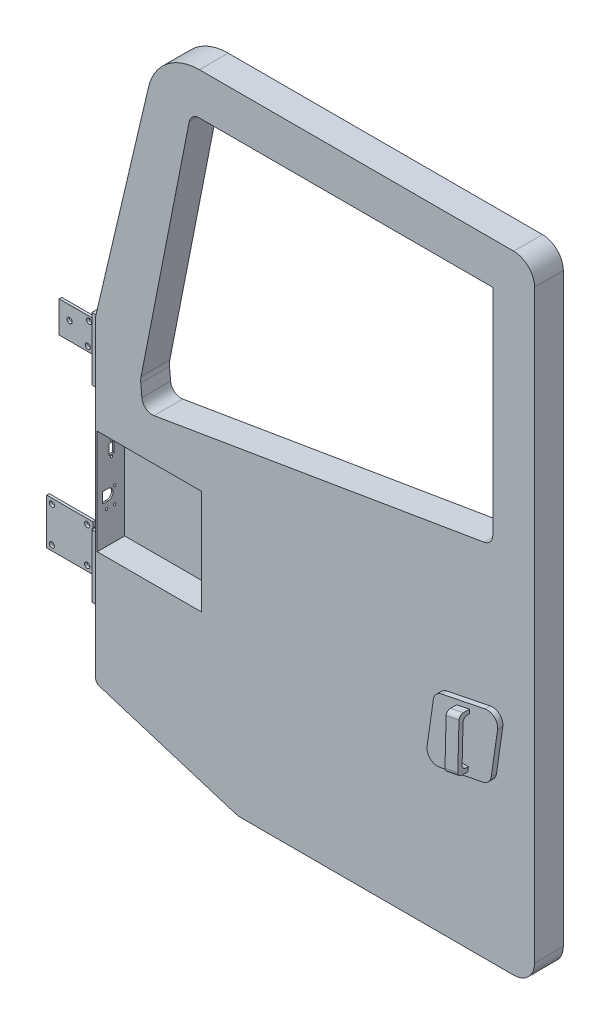
SolidWorks part; units mm, degrees
ref_plane "Front Plane" through (0, 0, 0) normal (0, 0, 1) x (1, 0, 0)
ref_plane "Top Plane" through (0, 0, 0) normal (0, 1, 0) x (1, 0, 0)
ref_plane "Right Plane" through (0, 0, 0) normal (1, 0, 0) x (0, 0, -1)
sketch "Sketch2" plane through (0, 0, 0) normal (0, 0, 1) x (1, 0, 0)
  line L1 (-179.7693, -762.022) -> (482.6, -762.022)
  line L3 (-281.2299, 761.978) -> (482.6, 761.978)
  line L4 (533.4, -711.222) -> (533.4, 711.178)
  line L5 (-459.8603, -656.939) -> (-452.0517, -645.784) construction
  line L6 (-417.9715, 597.0829) -> (44.2876, -63.266) construction
  line L8 (-524.4721, -657.2008) -> (-194.8579, -759.7295)
  line L9 (-306.1723, 639.7777) -> (-423.0219, 45.4039)
  line L10 (-423.7768, 31.1096) -> (-421.1458, 1.4921)
  line L14 (-281.2299, 660.378) -> (431.8, 660.378)
  line L16 (431.7996, 138.4174) -> (431.8, 660.378)
  line L17 (431.8, -660.422) -> (431.8, 660.378) construction
  line L18 (-172.0509, -660.422) -> (431.8, -660.422) construction
  line L19 (-533.4, 116.926) -> (-405.8883, 659.253)
  line L20 (-367.7549, -599.547) -> (-172.0509, -660.422) construction
  line L21 (-55.7209, -79.6007) -> (521.0599, 744.3665) construction
  line L22 (-306.1723, 639.7777) -> (-424.4164, 38.3105) construction
  line L23 (-424.4164, 38.3105) -> (-367.7549, -599.547) construction
  line L24 (-414.3579, -691.4526) -> (-194.8579, -759.7295) construction
  line L25 (-179.7693, -762.022) -> (482.6, -762.022)
  line L27 (-281.2299, 761.978) -> (482.6, 761.978)
  line L28 (533.4, -711.222) -> (533.4, 711.178)
  line L29 (-459.8603, -656.939) -> (-452.0517, -645.784) construction
  line L30 (-417.9715, 597.0829) -> (44.2876, -63.266) construction
  line L31 (-533.4, 116.926) -> (-466.2749, -638.723) construction
  line L32 (-391.6402, -21.3099) -> (410.6048, 113.3679)
  line L33 (-55.7209, -79.6007) -> (521.0599, 744.3665) construction
  line L34 (-281.2299, 761.978) -> (482.6, 761.978)
  line L35 (-533.4, 116.926) -> (-533.4, -645.074)
  line L36 (-179.7693, -762.022) -> (482.6, -762.022)
  line L37 (533.4, 711.178) -> (533.4, -711.222)
  line L38 (-417.9715, 597.0829) -> (44.2876, -63.266) construction
  line L39 (-471.5639, -673.6583) -> (-452.0517, -645.784) construction
  line L40 (-405.8883, 659.253) -> (-528.8132, 33.9764) construction
  line L41 (-55.7209, -79.6007) -> (521.0599, 744.3665) construction
  arc A0 (-405.8883, 659.253) -> (-281.2299, 761.978) centre (-281.2299, 634.978) cw
  arc A3 (533.4, 711.178) -> (482.6, 761.978) centre (482.6, 711.178) ccw
  arc A4 (482.6, -762.022) -> (533.4, -711.222) centre (482.6, -711.222) ccw
  arc A5 (-194.8579, -759.7295) -> (-179.7693, -762.022) centre (-179.7693, -711.222) ccw
  arc A7 (-367.7549, -599.547) -> (-367.7549, -599.547) centre (-367.7549, -599.547) ccw
  arc A8 (-172.0509, -660.422) -> (-172.0509, -660.422) centre (-172.0509, -660.422) ccw
  arc A9 (431.8, -660.422) -> (431.8, -660.422) centre (431.8, -660.422) ccw
  arc A10 (431.8, 660.378) -> (431.8, 660.378) centre (431.8, 660.378) ccw
  arc A11 (-306.1723, 639.7777) -> (-281.2299, 660.378) centre (-281.2299, 634.978) cw
  arc A12 (-423.0219, 45.4039) -> (-423.7768, 31.1096) centre (-373.176, 35.6045) ccw
  arc A13 (-424.4164, 38.3105) -> (-424.4164, 38.3105) centre (-424.4164, 38.3105) ccw construction
  arc A16 (-466.2749, -638.723) -> (-414.3579, -691.4526) centre (-391.0208, -616.5518) ccw construction
  arc A17 (-533.4, -645.074) -> (-524.4721, -657.2008) centre (-520.7, -645.074) ccw
  arc A18 (-528.8132, 33.9764) -> (-533.4, 116.926) centre (-501.9071, 77.0658) ccw construction
  arc A19 (431.7996, 138.4174) -> (410.6048, 113.3679) centre (406.3996, 138.4174) cw
  arc A20 (-391.6402, -21.3099) -> (-421.1458, 1.4921) centre (-395.8454, 3.7395) cw
  point P0 (0, 0)
  point P16 (-533.4, -0.0244)
  point P56 (0, 0)
  point P61 (0, 0)
  dimension "D3" = 127
  dimension "D6" = 50.8
  dimension "D8" = 50.8
  dimension "D2" = 12.7
  dimension "D9" = 25.4
  dimension "D1" = 1066.8
  dimension "D4" = 1524
  dimension "D5" = 762
  dimension "D7" = 101.6
extrude "Boss-Extrude1" add sketch "Sketch2" along normal mid plane 69.85 contours L8 A5 L1 A4 L4 A3 L3 A0 L10 A12 L9 A11 L14 L16 A20 region at (22.1716, -171.0663, 0)
ref_plane "bottom" through (0, -762.022, 0) normal (0, -1, 0) x (-1, 0, 0)
ref_plane "top door check" through (0, -158.772, 0) normal (0, -1, 0) x (-1, 0, 0)
ref_plane "door check mid" through (0, -176.2345, 0) normal (0, -1, 0) x (-1, 0, 0)
ref_plane "bottom door check" through (0, -193.697, 0) normal (0, -1, 0) x (-1, 0, 0)
ref_plane "top hinge top hole" through (0, 66.653, 0) normal (0, -1, 0) x (-1, 0, 0)
ref_plane "top hinge middle hole" through (0, 44.428, 0) normal (0, -1, 0) x (-1, 0, 0)
ref_plane "top hinge bottom hole" through (0, 12.678, 0) normal (0, -1, 0) x (-1, 0, 0)
ref_plane "bottome hinge top hole" through (0, -363.5595, 0) normal (0, -1, 0) x (-1, 0, 0)
ref_plane "bottom hinge bottom hole" through (0, -449.2845, 0) normal (0, -1, 0) x (-1, 0, 0)
ref_plane "Plane1" through (0, 0, 31.75) normal (0, 0, 1) x (1, 0, 0)
sketch "Sketch3" plane through (0, 0, 34.925) normal (0, 0, 1) x (1, 0, 0)
  line L0 (320.1959, -245.101) -> (425.9265, -223.6716)
  line L3 (314.9201, -401.6691) -> (420.6507, -380.2397)
  line L4 (456.113, -252.1835) -> (440.7462, -358.9639)
  line L5 (300.1004, -266.3768) -> (284.7336, -373.1572)
  line L6 (310.4001, -194.8067) -> (287.3499, -354.9772) construction
  line L7 (-487.6326, -408.8312) -> (533.4008, -201.8888) construction
  line L8 (-457.3598, -558.1943) -> (563.6737, -351.2518) construction
  line L9 (461.2461, -216.515) -> (438.1959, -376.6855) construction
  line L10 (373.0612, -234.3863) -> (367.7854, -390.9544) construction
  line L11 (360.2667, -236.9795) -> (354.9908, -393.5476)
  line L12 (385.8558, -231.7931) -> (380.58, -388.3612)
  line L13 (360.3684, -233.9586) -> (355.0926, -390.5267) construction
  line L14 (385.754, -234.814) -> (380.4782, -391.3821) construction
  arc A0 (300.1004, -266.3768) -> (320.1959, -245.101) centre (325.2414, -269.9949) cw
  arc A1 (284.7336, -373.1572) -> (314.9201, -401.6691) centre (309.8746, -376.7752) ccw
  arc A2 (440.7462, -358.9639) -> (420.6507, -380.2397) centre (415.6052, -355.3458) cw
  arc A3 (456.113, -252.1835) -> (425.9265, -223.6716) centre (430.972, -248.5655) ccw
  dimension "D3" = 25.4
  dimension "D1" = 152.4
  dimension "D2" = 152.4
  dimension "D4" = 12.7
  dimension "D5" = 12.7
extrude "Boss-Extrude2" add sketch "Sketch3" along normal blind 12.7 contours L5 A1 L3 L11 L0 A0 | L4 A3 L0 L12 L3 A2 | L12 L0 L11 L3 region at (325.2101, -323.7797, 34.925) region at (370.4233, -312.6704, 34.925) region at (415.6365, -301.561, 34.925)
sketch "Sketch5" plane through (0, 0, 34.925) normal (0, 0, 1) x (1, 0, 0)
  line L6 (-179.7693, -762.022) -> (482.6, -762.022)
  line L12 (-179.7693, -762.022) -> (482.6, -762.022)
  line L28 (387.9598, -243.0291) -> (384.7172, -375.8602)
  line L29 (353.4927, -382.1888) -> (356.7353, -249.3577)
  line L30 (387.9598, -243.0291) -> (356.7353, -249.3577)
  line L31 (384.7172, -375.8602) -> (353.4927, -382.1888)
  line L32 (320.1959, -245.101) -> (425.9265, -223.6716) construction
  line L33 (314.9201, -401.6691) -> (420.6507, -380.2397) construction
  line L34 (320.1959, -245.101) -> (425.9265, -223.6716) construction
  line L35 (314.9201, -401.6691) -> (420.6507, -380.2397) construction
  dimension "D2" = 11.43
  dimension "D3" = 11.43
  dimension "D1" = 0
extrude "Boss-Extrude4" add sketch "Sketch5" along normal blind 38.1 contours L31 L28 L30 L29 region at (370.7262, -312.609, 34.925)
sketch "Sketch6" plane through (393.6581, -9.61, 0) normal (0.9997, -0.0244, 0) x (0, 0, -1)
  line L9 (-47.625, -356.1994) -> (-62.865, -356.1994)
  line L10 (-62.865, -356.1994) -> (-62.865, -243.6487)
  line L11 (-62.865, -243.6487) -> (-47.625, -243.6487)
  line L12 (-47.625, -356.1994) -> (-62.865, -356.1994)
  line L13 (-62.865, -356.1994) -> (-62.865, -243.6487)
  line L14 (-62.865, -243.6487) -> (-47.625, -243.6487)
  line M5 (-47.625, -366.3594) -> (-47.625, -233.4887)
  dimension "D1" = 10.16
extrude "Cut-Extrude6" cut sketch "Sketch6" against normal through all and the other way through all contours L14 L13 L12 M5 region at (386.3385, -309.4447, 55.245)
fillet "Fillet5" radius 10.16 4 edges at (369.1049, -379.0245, 73.025) (369.4394, -365.3242, 62.865) (372.1861, -252.8071, 62.865) (372.3476, -246.1934, 73.025)
sketch "Sketch7" plane through (-533.4, 59.3738, 0) normal (1, 0, 0) x (0, 0, 1)
  line L0 (0, 821.3958) -> (0, -702.6042) construction
  line L1 (34.925, 821.3958) -> (-34.925, 821.3958) construction
  line L2 (34.925, -702.6042) -> (-34.925, -702.6042) construction
  line L4 (-31.75, -57.5522) -> (31.75, -57.5522)
  line L5 (-31.75, -57.5522) -> (-31.75, 94.8478)
  line L6 (-31.75, 94.8478) -> (31.75, 94.8478)
  line L11 (31.75, -57.5522) -> (31.75, 94.8478)
  line L12 (-31.75, -57.5522) -> (31.75, 94.8478) construction
  line L13 (-31.75, 94.8478) -> (31.75, -57.5522) construction
  line L19 (34.925, -57.5522) -> (-34.925, -57.5522) construction
  line L21 (-31.75, 552.0478) -> (31.75, 552.0478)
  line L28 (-31.75, 552.0478) -> (-31.75, 399.6478)
  line L29 (-31.75, 399.6478) -> (31.75, 399.6478)
  line L30 (31.75, 552.0478) -> (31.75, 399.6478)
  line L31 (-31.75, 552.0478) -> (31.75, 399.6478) construction
  line L32 (-31.75, 399.6478) -> (31.75, 552.0478) construction
  point P6 (0, 18.6478)
  point P13 (0, 475.8478)
  dimension "D1" = 63.5
  dimension "D2" = 152.4
  dimension "D4" = 304.8
extrude "Boss-Extrude5" add sketch "Sketch7" against normal blind 12.7
sketch "Sketch16" plane through (0, 0, 34.925) normal (0, 0, 1) x (1, 0, 0)
  line L1 (-529.59, -122.9099) -> (-529.59, -376.9099)
  line L3 (-275.59, -376.9099) -> (-275.59, -122.9099)
  line L5 (-533.4, 116.926) -> (-533.4, -645.074) construction
  line L6 (-529.59, -122.9099) -> (-275.59, -122.9099)
  line L7 (-529.59, -376.9099) -> (-275.59, -376.9099)
  dimension "D1" = 254
  dimension "D2" = 101.6
  dimension "D3" = 254
  dimension "D4" = 3.81
extrude "Cut-Extrude8" cut sketch "Sketch16" against normal blind 66.675
sketch "Sketch20" plane through (-533.4, 0, 0) normal (-1, 0, 0) x (0, 0, 1)
  line L0 (-38.4175, -176.2345) -> (38.4175, -176.2345) construction
  line L1 (-6.35, -188.9345) -> (6.35, -188.9345)
  line L2 (-6.35, -188.9345) -> (-6.35, -163.5345)
  line L3 (-6.35, -163.5345) -> (6.35, -163.5345)
  line L4 (6.35, -188.9345) -> (6.35, -163.5345)
  line L5 (-6.35, -188.9345) -> (6.35, -163.5345) construction
  line L6 (-6.35, -163.5345) -> (6.35, -188.9345) construction
  line L7 (-38.4175, -158.772) -> (38.4175, -158.772) construction
  line L8 (6.35, -176.2345) -> (-6.35, -176.2345) construction
  circle A0 centre (0, -158.772) radius 2.54
  circle A1 centre (0, -193.697) radius 2.54
  point P0 (0, -176.2345)
  dimension "D3" = 5.08
  dimension "D1" = 12.7
  dimension "D2" = 25.4
extrude "Cut-Extrude12" cut sketch "Sketch20" against normal up to surface (3.81 mm away) contours A0 | L4 L3 L2 L1 | A1 up to face at (-529.59, -249.9099, 1.5875)
sketch "Sketch21" plane through (0, 0, 0) normal (0, 0, 1) x (1, 0, 0)
  line L0 (-38.4175, 66.653) -> (38.4175, 66.653) construction
  line L1 (-202.423, 66.653) -> (-1027.3811, 66.653) construction
  line L2 (-212.5576, 44.428) -> (-1027.3811, 44.428) construction
  line L3 (-38.4175, 44.428) -> (38.4175, 44.428) construction
  line L4 (-212.5576, 12.678) -> (-1027.3811, 12.678) construction
  line L5 (-38.4175, 12.678) -> (38.4175, 12.678) construction
  line L6 (-546.1, 116.926) -> (-546.1, -35.474) construction
  line L7 (-558.8, 66.653) -> (-546.1, 66.653)
  line L8 (-558.8, 66.653) -> (-558.8, 12.678)
  line L9 (-558.8, 12.678) -> (-546.1, 12.678)
  line L10 (-546.1, 66.653) -> (-546.1, 12.678)
  line L11 (-654.05, 77.448) -> (-654.05, 1.248)
  line L12 (-654.05, 77.448) -> (-558.8, 77.448)
  line L15 (-558.8, 77.448) -> (-558.8, 12.678)
  line L16 (-654.05, 77.448) -> (-558.8, 12.678) construction
  line L17 (-654.05, 10.0872) -> (-558.8, 77.448) construction
  line L18 (-654.05, 1.248) -> (-558.8, 1.248)
  line L19 (-558.8, 12.678) -> (-558.8, 1.248)
  circle A0 centre (-584.2, 12.678) radius 6.35
  circle A1 centre (-628.65, 44.428) radius 6.35
  circle A2 centre (-581.025, 66.653) radius 6.35
  point P18 (-605.4912, 44.428)
  dimension "D2" = 12.7
  dimension "D3" = 25.4
  dimension "D4" = 69.85
  dimension "D5" = 22.225
  dimension "D6" = 95.25
  dimension "D9" = 64.77
  dimension "D1" = 12.7
  dimension "D7" = 76.2
  dimension "D8" = 33.02
extrude "Boss-Extrude8" add sketch "Sketch21" along normal mid plane 6.35 contours L19 L8 L15 L12 L11 L18 A2 A1 A0 | L10 L7 L8 L9 region at (-552.45, 39.6655, 0) region at (-606.8928, 39.2427, 0)
sketch "Sketch26" plane through (0, 0, 0) normal (0, 0, 1) x (1, 0, 0)
  line L0 (-193.6896, -363.5595) -> (-881.8717, -363.5595) construction
  line L1 (-38.4175, -363.5595) -> (38.4175, -363.5595) construction
  line L2 (-133.4597, -449.2845) -> (-881.8717, -449.2845) construction
  line L3 (-38.4175, -449.2845) -> (38.4175, -449.2845) construction
  line L4 (-625.8948, -363.5595) -> (-625.8948, -449.2845) construction
  line L5 (-625.8948, -406.422) -> (-892.4677, -406.422) construction
  line L6 (-546.1, -340.274) -> (-546.1, -492.674) construction
  line L7 (-571.5, -449.2845) -> (-546.1, -449.2845)
  line L8 (-571.5, -449.2845) -> (-571.5, -363.5595)
  line L9 (-571.5, -363.5595) -> (-546.1, -363.5595)
  line L10 (-546.1, -449.2845) -> (-546.1, -363.5595)
  line L11 (-571.5, -449.2845) -> (-546.1, -363.5595) construction
  line L12 (-571.5, -363.5595) -> (-546.1, -449.2845) construction
  point P12 (-558.8, -406.422)
  dimension "D1" = 25.4
extrude "Boss-Extrude12" add sketch "Sketch26" along normal mid plane 12.7
sketch "Sketch27" plane through (0, 0, 0) normal (0, 0, 1) x (1, 0, 0)
  line L0 (-211.2814, -363.5595) -> (-919.4505, -363.5595) construction
  line L1 (-38.4175, -363.5595) -> (38.4175, -363.5595) construction
  line L2 (-201.3631, -449.2845) -> (-928.7076, -449.2845) construction
  line L3 (-38.4175, -449.2845) -> (38.4175, -449.2845) construction
  line L4 (-571.5, -363.5595) -> (-571.5, -449.2845) construction
  line L5 (-631.7994, -363.5595) -> (-631.7994, -449.2845) construction
  line L6 (-631.7994, -406.422) -> (-919.4505, -406.422) construction
  line L8 (-684.2125, -461.9845) -> (-571.5, -461.9845)
  line L9 (-684.2125, -461.9845) -> (-684.2125, -350.8595)
  line L10 (-684.2125, -350.8595) -> (-571.5, -350.8595)
  line L11 (-571.5, -461.9845) -> (-571.5, -350.8595)
  line L12 (-684.2125, -461.9845) -> (-571.5, -350.8595) construction
  line L13 (-684.2125, -350.8595) -> (-571.5, -461.9845) construction
  circle A0 centre (-585.7875, -363.5595) radius 6.35
  circle A2 centre (-671.5125, -449.2845) radius 6.35
  circle A4 centre (-585.7875, -449.2845) radius 6.35
  circle A5 centre (-671.5125, -363.5595) radius 6.35
  point P22 (-627.8563, -406.422)
  dimension "D1" = 12.7
  dimension "D2" = 100.0125
  dimension "D3" = 14.2875
  dimension "D4" = 12.7
extrude "Boss-Extrude13" add sketch "Sketch27" along normal mid plane 6.35
sketch "Sketch28" plane through (-533.4, 0, 0) normal (-1, 0, 0) x (0, 0, 1)
  line L1 (9.225, -256.897) -> (22.225, -256.897)
  line L3 (9.225, -282.897) -> (22.225, -282.897)
  line L4 (22.225, -256.897) -> (22.225, -282.897)
  line L5 (34.925, -245.101) -> (34.925, -223.6716) construction
  line L6 (-38.4175, -193.697) -> (38.4175, -193.697) construction
  arc A6 (9.225, -256.897) -> (9.225, -282.897) centre (9.225, -269.897) ccw
  circle A7 centre (-7.705, -258.147) radius 3
  circle A8 centre (-7.705, -298.147) radius 3
  circle A9 centre (12.295, -298.147) radius 3
  point P7 (-3.775, -269.897)
  point P16 (22.225, -269.897)
  dimension "D4" = 40
  dimension "D5" = 26
  dimension "D6" = 26
  dimension "D1" = 11.75
  dimension "D2" = 3.93
  dimension "D3" = 20
  dimension "D8" = 12.7
  dimension "D7" = 6
  dimension "D9" = 13
  dimension "D10" = 76.2
extrude "Cut-Extrude13" cut sketch "Sketch28" against normal up to surface (3.81 mm away) contours L1 A6 L3 L4 | A8 | A9 | A7 region at (-533.4, -269.897, 10.4385) region at (-533.4, -298.147, -7.705) region at (-533.4, -298.147, 12.295) up to face at (-529.59, -176.2345, 0)
equation "\"doorwidth\"= 42in"
equation "\"D1@Sketch2\"=\"doorwidth\""
equation "\"doorheight\"= 60in"
equation "\"D4@Sketch2\"=\"doorheight\""
equation "\"doorthickness\"= 2.75in"
equation "\"D1@Boss-Extrude1\"=\"doorthickness\""
equation "\"hingewidth\"= 2.5in"
equation "\"hingeheight\"= 6in"
equation "\"distanceofhinges\"= 12in"
equation "\"D1@Sketch7\"=\"hingewidth\""
equation "\"D2@Sketch7\"=\"hingeheight\""
equation "\"D4@Sketch7\"=\"distanceofhinges\""
